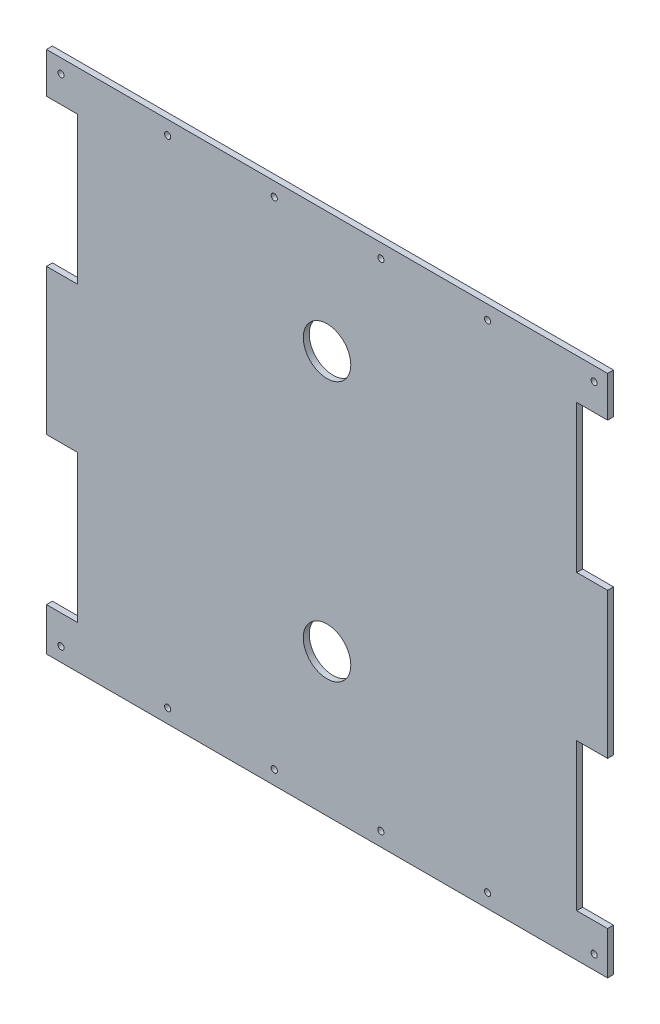
SolidWorks part; units mm, degrees
material "PBT General Purpose"
ref_plane "Front" through (0, 0, 0) normal (0, 0, 1) x (1, 0, 0)
ref_plane "Top" through (0, 0, 0) normal (0, 1, 0) x (1, 0, 0)
ref_plane "Right" through (0, 0, 0) normal (1, 0, 0) x (0, 0, -1)
sketch "Sketch5" plane through (0, 0, 0) normal (0, 0, 1) x (1, 0, 0)
  line L0 (47.1246, -7.4523) -> (30.6146, -7.4523)
  line L1 (-252.8494, 249.5587) -> (47.1246, 249.5587)
  line L2 (-252.8494, 249.5587) -> (-252.8494, 227.8859)
  line L3 (-252.8494, -30.3493) -> (47.1246, -30.3493)
  line L4 (47.1246, 249.5587) -> (47.1246, 227.8859)
  line L5 (30.6146, -7.4523) -> (30.6146, 71.2877)
  line L6 (30.6146, 71.2877) -> (47.1246, 71.2877)
  line L8 (47.1246, -7.4523) -> (47.1246, -30.3493)
  line L9 (47.1246, 149.1459) -> (30.6146, 149.1459)
  line L10 (30.6146, 149.1459) -> (30.6146, 227.8859)
  line L11 (30.6146, 227.8859) -> (47.1246, 227.8859)
  line L13 (47.1246, 149.1459) -> (47.1246, 71.2877)
  line L14 (-252.8494, 227.8859) -> (-236.3394, 227.8859)
  line L15 (-236.3394, 227.8859) -> (-236.3394, 149.1459)
  line L16 (-236.3394, 149.1459) -> (-252.8494, 149.1459)
  line L18 (-252.8494, 149.1459) -> (-252.8494, 71.2877)
  line L19 (-252.8494, 71.2877) -> (-236.3394, 71.2877)
  line L20 (-236.3394, 71.2877) -> (-236.3394, -7.4523)
  line L21 (-236.3394, -7.4523) -> (-252.8494, -7.4523)
  line L23 (-252.8494, -7.4523) -> (-252.8494, -30.3493)
  line L24 (47.1246, -22.8907) -> (-72.4065, -22.8907) construction
  line L25 (-252.8494, 242.1016) -> (47.1246, 242.1016) construction
  line L26 (-75.7065, -22.8907) -> (-252.8494, -22.8907) construction
  circle A8 centre (39.9435, -22.8907) radius 1.65
  circle A10 centre (-17.0565, -22.8907) radius 1.65
  circle A11 centre (-74.0565, -22.8907) radius 1.65
  circle A12 centre (-131.0565, -22.8907) radius 1.65
  circle A13 centre (-188.0565, -22.8907) radius 1.65
  circle A14 centre (-245.0565, -22.8907) radius 1.65
  circle A15 centre (39.9435, 242.1016) radius 1.65
  circle A16 centre (-17.0565, 242.1016) radius 1.65
  circle A17 centre (-74.0565, 242.1016) radius 1.65
  circle A18 centre (-131.0565, 242.1016) radius 1.65
  circle A19 centre (-188.0565, 242.1016) radius 1.65
  circle A20 centre (-245.0565, 242.1016) radius 1.65
  circle A22 centre (-102.8624, 184.8543) radius 12.7
  circle A23 centre (-102.8624, 45.8507) radius 12.7
  point P12 (38.8696, 149.1459)
  point P55 (0, 0)
  dimension "D10" = 3.3
  dimension "D12" = 3.3
  dimension "D14" = 25.4
  dimension "D15" = 25.4
  dimension "D1" = 299.974
  dimension "D2" = 279.908
  dimension "D3" = 16.51
  dimension "D4" = 16.51
  dimension "D5" = 16.51
  dimension "D6" = 78.74
  dimension "D7" = 78.74
  dimension "D8" = 78.74
  dimension "D9" = 16.51
  dimension "D16" = 76.2
  dimension "D11" = 6
  dimension "D13" = 6
extrude "Boss-Extrude1" add sketch "Sketch5" along normal blind 3.175
